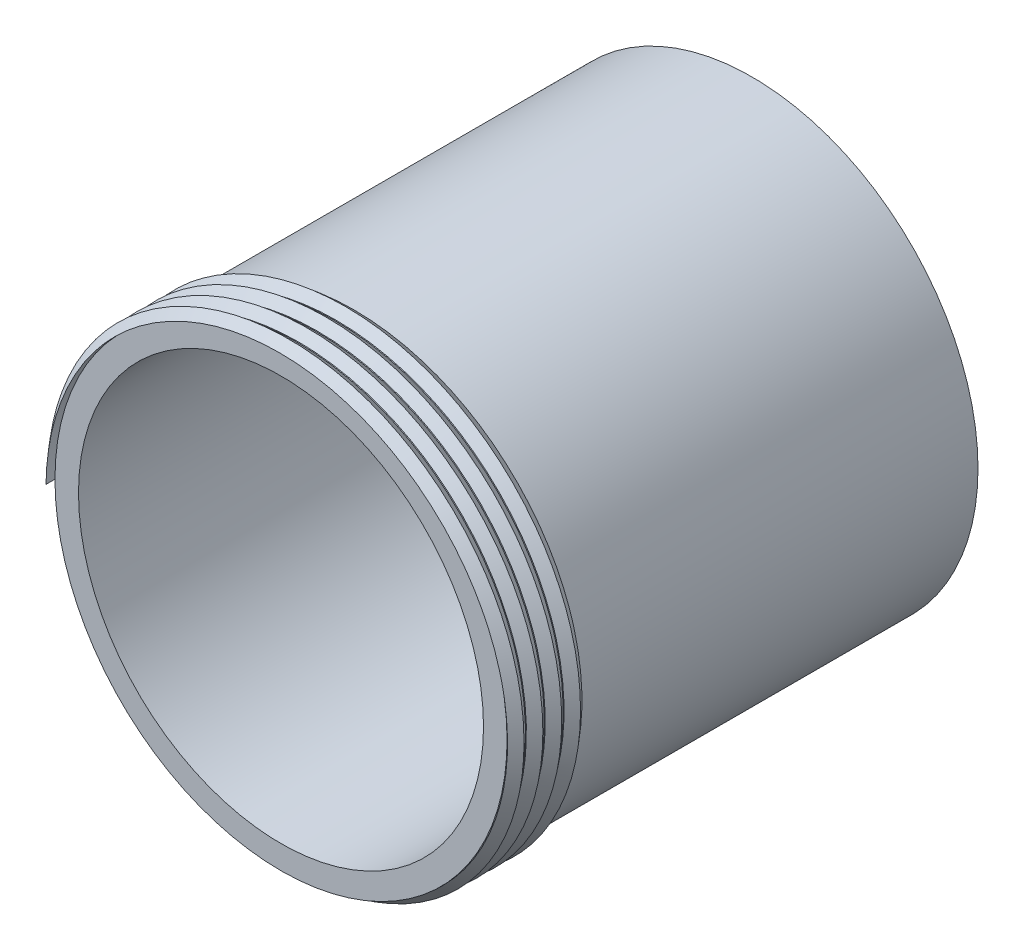
SolidWorks part; units mm, degrees
ref_plane "Front Plane" through (0, 0, 0) normal (0, 0, 1) x (1, 0, 0)
ref_plane "Top Plane" through (0, 0, 0) normal (0, 1, 0) x (1, 0, 0)
ref_plane "Right Plane" through (0, 0, 0) normal (1, 0, 0) x (0, 0, -1)
sketch "Sketch1" plane through (0, 0, 0) normal (0, 0, 1) x (1, 0, 0)
  circle A0 centre (0, 0) radius 27.305 construction
  circle A1 centre (0, 0) radius 30.48
  dimension "D1" = 54.61
  dimension "D2" = 3.175
extrude "Boss-Extrude1" add sketch "Sketch1" along normal blind 63.5
sketch "Sketch2" plane through (0, 0, 63.5) normal (0, 0, 1) x (1, 0, 0)
  circle A2 centre (0, 0) radius 27.305
  circle A3 centre (0, 0) radius 27.305
  dimension "D1" = 3.175
extrude "Cut-Extrude4" cut sketch "Sketch2" against normal blind 45.274 from offset 3.175
sketch "Sketch3" plane through (0, 0, 63.5) normal (0, 0, 1) x (1, 0, 0)
  circle A0 centre (0, 0) radius 30.48
  circle A1 centre (0, 0) radius 30.48 construction
curve "Helix/Spiral2" pitch 2.54 height 10.16 radius 30.48 centre (0, 0, 63.5) axis (0, 0, -1) start towards (-1, 0, 0)
sketch "Threading Cutting Tool" plane through (0, 0, 0) normal (0, 1, 0) x (1, 0, 0)
  line L0 (-30.48, -63.5) -> (-30.48, -51.9179)
  line L1 (-30.48, 0) -> (-30.48, -63.5) construction
  line L2 (-30.48, -63.5) -> (-31.496, -63.5)
  line L3 (-30.48, -63.5) -> (30.48, -63.5) construction
  line L4 (-31.496, -63.5) -> (-30.48, -64.7065)
  line L5 (-30.48, -64.7065) -> (-30.48, -62.2935)
  line L6 (-31.496, -63.5) -> (-30.48, -62.2935)
  dimension "D1" = 1.016
  dimension "D2" = 2.413
sweep "Sweep1" add profiles "Threading Cutting Tool" path "Helix/Spiral2"
